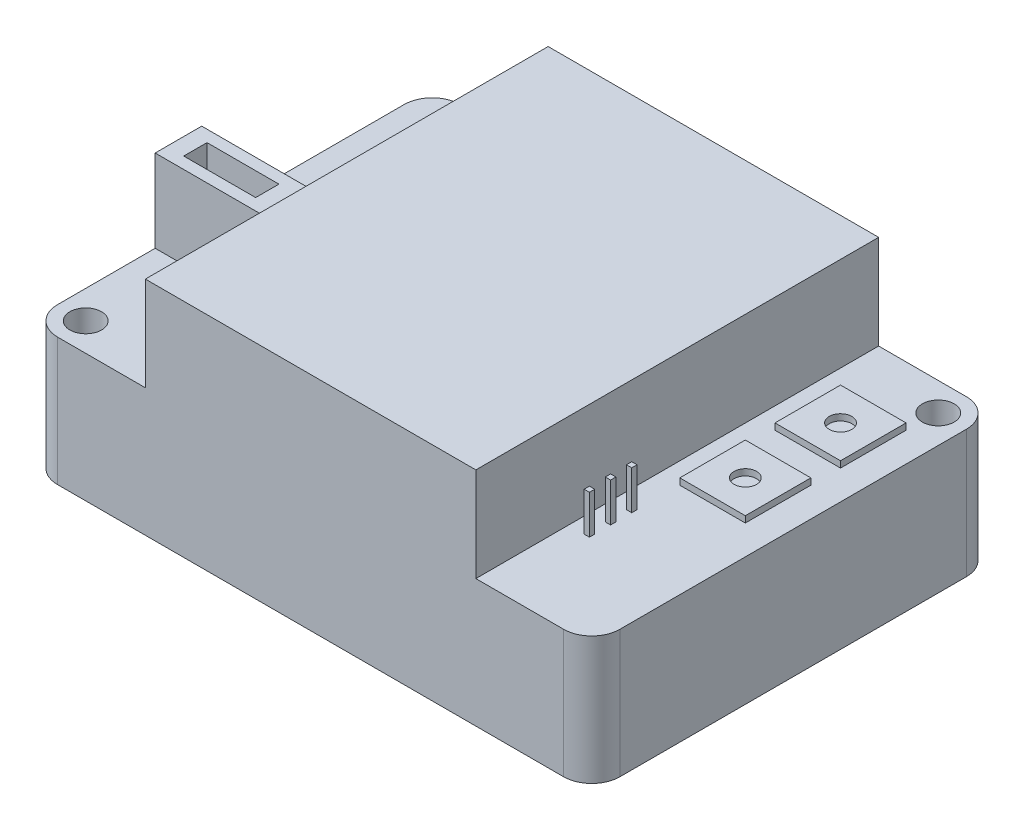
SolidWorks part; units mm, degrees
ref_plane "Front Plane" through (0, 0, 0) normal (0, 0, 1) x (1, 0, 0)
ref_plane "Top Plane" through (0, 0, 0) normal (0, 1, 0) x (1, 0, 0)
ref_plane "Right Plane" through (0, 0, 0) normal (1, 0, 0) x (0, 0, -1)
sketch "Sketch1" plane through (0, 0, 0) normal (0, 0, 1) x (1, 0, 0)
  line L1 (0, 0) -> (67.5157, 0)
  line L2 (0, 0) -> (0, 15.3416)
  line L3 (13.9167, 26.6446) -> (53.5991, 26.6446)
  line L4 (67.5157, 0) -> (67.5157, 15.3416)
  line L7 (0, 15.3416) -> (13.9167, 15.3416)
  line L8 (13.9167, 26.6446) -> (13.9167, 15.3416)
  line L11 (67.5157, 15.3416) -> (53.5991, 15.3416)
  line L12 (53.5991, 26.6446) -> (53.5991, 15.3416)
  dimension "D1" = 67.5157
  dimension "D2" = 15.3416
  dimension "D3" = 26.6446
  dimension "D4" = 13.9167
extrude "Boss-Extrude1" add sketch "Sketch1" against normal blind 48.3616
fillet "Fillet1" radius 3.3782 4 edges at (0, 7.6708, -48.3616) (67.5157, 7.6708, -48.3616) (67.5157, 7.6708, 0) (0, 7.6708, 0)
sketch "Sketch2" plane through (0, 15.3416, 0) normal (0, 1, 0) x (1, 0, 0)
  circle A0 centre (3.3782, 3.3782) radius 1.905
  circle A1 centre (64.1375, 44.9834) radius 1.905
  dimension "D1" = 3.81
extrude "Cut-Extrude1" cut sketch "Sketch2" against normal through all
sketch "Sketch3" plane through (0, 15.3416, 0) normal (0, 1, 0) x (1, 0, 0)
  line L0 (3.5154, 48.3616) -> (3.5154, 0) construction
  line L1 (13.9167, 48.3616) -> (3.3782, 48.3616) construction
  line L2 (13.9167, 0) -> (3.3782, 0) construction
  line L3 (0, 44.9834) -> (0, 3.3782) construction
  line L4 (33.7579, 48.3616) -> (33.7579, 0) construction
  line L5 (53.5991, 48.3616) -> (13.9167, 48.3616) construction
  line L6 (53.5991, 0) -> (13.9167, 0) construction
  line L7 (56.1315, 21.9532) -> (56.1315, 29.8221)
  line L8 (3.5154, 33.3832) -> (11.3843, 33.3832)
  line L9 (3.5154, 33.3832) -> (3.5154, 41.2521)
  line L10 (3.5154, 41.2521) -> (11.3843, 41.2521)
  line L11 (11.3843, 33.3832) -> (11.3843, 41.2521)
  line L12 (3.5154, 21.9532) -> (11.3843, 21.9532)
  line L13 (3.5154, 21.9532) -> (3.5154, 29.8221)
  line L14 (3.5154, 29.8221) -> (11.3843, 29.8221)
  line L15 (11.3843, 21.9532) -> (11.3843, 29.8221)
  line L16 (64.0004, 33.3832) -> (56.1315, 33.3832)
  line L17 (64.0004, 21.9532) -> (56.1315, 21.9532)
  line L18 (64.0004, 21.9532) -> (64.0004, 29.8221)
  line L19 (64.0004, 29.8221) -> (56.1315, 29.8221)
  line L20 (64.0004, 33.3832) -> (64.0004, 41.2521)
  line L21 (56.1315, 33.3832) -> (56.1315, 41.2521)
  line L22 (64.0004, 41.2521) -> (56.1315, 41.2521)
  line L23 (3.5154, 33.3832) -> (11.3843, 41.2521) construction
  line L24 (3.5154, 21.9532) -> (11.3843, 29.8221) construction
  circle A0 centre (7.4498, 37.3177) radius 1.3525
  circle A1 centre (7.4498, 25.8877) radius 1.3525
  circle A2 centre (60.0659, 25.8877) radius 1.3525
  circle A3 centre (60.0659, 37.3177) radius 1.3526
  dimension "D5" = 2.7051
  dimension "D1" = 3.5154
  dimension "D2" = 7.1095
  dimension "D3" = 3.5611
  dimension "D4" = 7.8689
extrude "Boss-Extrude2" add sketch "Sketch3" along normal blind 0.762
sketch "Sketch4" plane through (0, 15.3416, 0) normal (0, 1, 0) x (1, 0, 0)
  line L0 (3.5154, 21.9532) -> (11.3843, 21.9532) construction
  line L1 (0, 15.0952) -> (12.7, 15.0952)
  line L2 (0, 15.0952) -> (0, 20.6832)
  line L3 (0, 20.6832) -> (12.7, 20.6832)
  line L4 (12.7, 15.0952) -> (12.7, 20.6832)
  line L5 (0, 15.0952) -> (12.7, 20.6832) construction
  line L6 (0, 20.6832) -> (12.7, 15.0952) construction
  line L7 (2.032, 16.4922) -> (10.668, 16.4922)
  line L8 (2.032, 16.4922) -> (2.032, 19.2862)
  line L9 (2.032, 19.2862) -> (10.668, 19.2862)
  line L10 (10.668, 16.4922) -> (10.668, 19.2862)
  line L11 (2.032, 16.4922) -> (10.668, 19.2862) construction
  line L12 (2.032, 19.2862) -> (10.668, 16.4922) construction
  line L13 (0, 44.9834) -> (0, 3.3782) construction
  point P0 (6.35, 17.8892)
  point P5 (6.35, 17.8892)
  dimension "D1" = 1.27
  dimension "D2" = 5.588
  dimension "D3" = 2.794
  dimension "D4" = 8.636
  dimension "D5" = 12.7
extrude "Boss-Extrude3" add sketch "Sketch4" along normal blind 9.906
sketch "Sketch5" plane through (0, 15.3416, 0) normal (0, 1, 0) x (1, 0, 0)
  line L0 (64.1375, 0) -> (53.5991, 0) construction
  line L1 (55.4787, 16.2027) -> (56.1137, 16.2027)
  line L2 (55.4787, 16.2027) -> (55.4787, 16.8377)
  line L3 (55.4787, 16.8377) -> (56.1137, 16.8377)
  line L4 (56.1137, 16.2027) -> (56.1137, 16.8377)
  line L5 (55.4787, 16.2027) -> (56.1137, 16.8377) construction
  line L6 (55.4787, 16.8377) -> (56.1137, 16.2027) construction
  line L7 (55.4787, 13.6627) -> (56.1137, 13.6627)
  line L8 (55.4787, 13.6627) -> (55.4787, 14.2977)
  line L9 (55.4787, 14.2977) -> (56.1137, 14.2977)
  line L10 (56.1137, 13.6627) -> (56.1137, 14.2977)
  line L11 (55.4787, 13.6627) -> (56.1137, 14.2977) construction
  line L12 (55.4787, 14.2977) -> (56.1137, 13.6627) construction
  line L13 (55.4787, 11.1227) -> (56.1137, 11.1227)
  line L14 (55.4787, 11.1227) -> (55.4787, 11.7577)
  line L15 (55.4787, 11.7577) -> (56.1137, 11.7577)
  line L16 (56.1137, 11.1227) -> (56.1137, 11.7577)
  line L17 (55.4787, 11.1227) -> (56.1137, 11.7577) construction
  line L18 (55.4787, 11.7577) -> (56.1137, 11.1227) construction
  line L19 (53.5991, 48.3616) -> (53.5991, 0) construction
  point P0 (55.7962, 16.5202)
  point P5 (55.7962, 13.9802)
  point P10 (55.7962, 11.4402)
  dimension "D1" = 2.54
  dimension "D2" = 2.54
  dimension "D3" = 0.635
  dimension "D4" = 11.1227
  dimension "D5" = 1.8796
extrude "Boss-Extrude4" add sketch "Sketch5" along normal blind 4.6736
sketch "Sketch6" plane through (0, 15.3416, 0) normal (0, 1, 0) x (1, 0, 0)
  line L0 (2.032, 17.8892) -> (10.668, 17.8892) construction
  line L1 (2.032, 19.2862) -> (2.032, 16.4922) construction
  line L2 (10.668, 16.4922) -> (10.668, 19.2862) construction
  line L3 (4.191, 19.2862) -> (4.191, 16.4922) construction
  line L4 (10.668, 19.2862) -> (2.032, 19.2862) construction
  line L5 (2.032, 16.4922) -> (10.668, 16.4922) construction
  line L6 (8.509, 19.2862) -> (8.509, 16.4922) construction
  line L7 (10.668, 19.2862) -> (2.032, 19.2862) construction
  line L8 (6.35, 19.2862) -> (6.35, 16.4922) construction
  line L9 (2.032, 16.4922) -> (10.668, 16.4922) construction
  line L11 (2.032, 19.2862) -> (2.032, 16.4922) construction
  line L12 (55.4787, 16.2027) -> (56.1137, 16.8377) construction
  line L13 (55.4787, 13.6627) -> (56.1137, 14.2977) construction
  line L14 (55.4787, 11.1227) -> (56.1137, 11.7577) construction
  point P20 (4.191, 17.8892)
  point P21 (6.35, 17.8892)
  point P22 (8.509, 17.8892)
  point P23 (7.4498, 37.3177)
  point P24 (7.4498, 25.8877)
  point P26 (60.0659, 37.3177)
  point P28 (60.0659, 25.8877)
  point P39 (55.7962, 13.9802)
  point P44 (55.7962, 11.4402)
  point P45 (55.7962, 16.5202)
sketch "0_0_Point" plane through (0, 15.3416, 0) normal (0, 1, 0) x (1, 0, 0)
  point P0 (7.4498, 25.8877)
other "0_0" parameters "Diameter"=2, "StubLength"=2
ref_axis "Axis1" through (7.4498, 25.3416, -25.8877) along (0, -1, 0)
sketch "1_0_Point" plane through (0, 15.3416, 0) normal (0, 1, 0) x (1, 0, 0)
  point P0 (7.4498, 37.3177)
other "1_0" parameters "Diameter"=2, "StubLength"=2
ref_axis "Axis2" through (7.4498, 25.3416, -37.3177) along (0, -1, 0)
sketch "2_0_Point" plane through (0, 15.3416, 0) normal (0, 1, 0) x (1, 0, 0)
  point P0 (60.0659, 25.8877)
other "2_0" parameters "Diameter"=2, "StubLength"=2
ref_axis "Axis3" through (60.0659, 25.3416, -25.8877) along (0, -1, 0)
sketch "3_0_Point" plane through (0, 15.3416, 0) normal (0, 1, 0) x (1, 0, 0)
  point P0 (60.0659, 37.3177)
other "3_0" parameters "Diameter"=2, "StubLength"=2
ref_axis "Axis4" through (60.0659, 25.3416, -37.3177) along (0, -1, 0)
sketch "4_0_Point" plane through (0, 15.3416, 0) normal (0, 1, 0) x (1, 0, 0)
  point P0 (4.191, 17.8892)
other "4_0" parameters "Diameter"=2, "StubLength"=2
ref_axis "Axis5" through (4.191, 25.3416, -17.8892) along (0, -1, 0)
sketch "4_1_Point" plane through (0, 15.3416, 0) normal (0, 1, 0) x (1, 0, 0)
  point P0 (6.35, 17.8892)
other "4_1" parameters "Diameter"=2, "StubLength"=2
ref_axis "Axis6" through (6.35, 25.3416, -17.8892) along (0, -1, 0)
sketch "4_2_Point" plane through (0, 15.3416, 0) normal (0, 1, 0) x (1, 0, 0)
  point P0 (8.509, 17.8892)
other "4_2" parameters "Diameter"=2, "StubLength"=2
ref_axis "Axis7" through (8.509, 25.3416, -17.8892) along (0, -1, 0)
sketch "5_0_Point" plane through (0, 15.3416, 0) normal (0, 1, 0) x (1, 0, 0)
  point P0 (55.7962, 11.4402)
other "5_0" parameters "Diameter"=2, "StubLength"=2
ref_axis "Axis8" through (55.7962, 25.3416, -11.4402) along (0, -1, 0)
sketch "5_1_Point" plane through (0, 15.3416, 0) normal (0, 1, 0) x (1, 0, 0)
  point P0 (55.7962, 13.9802)
other "5_1" parameters "Diameter"=2, "StubLength"=2
ref_axis "Axis9" through (55.7962, 25.3416, -13.9802) along (0, -1, 0)
sketch "5_2_Point" plane through (0, 15.3416, 0) normal (0, 1, 0) x (1, 0, 0)
  point P0 (55.7962, 16.5202)
other "5_2" parameters "Diameter"=2, "StubLength"=2
ref_axis "Axis10" through (55.7962, 25.3416, -16.5202) along (0, -1, 0)
